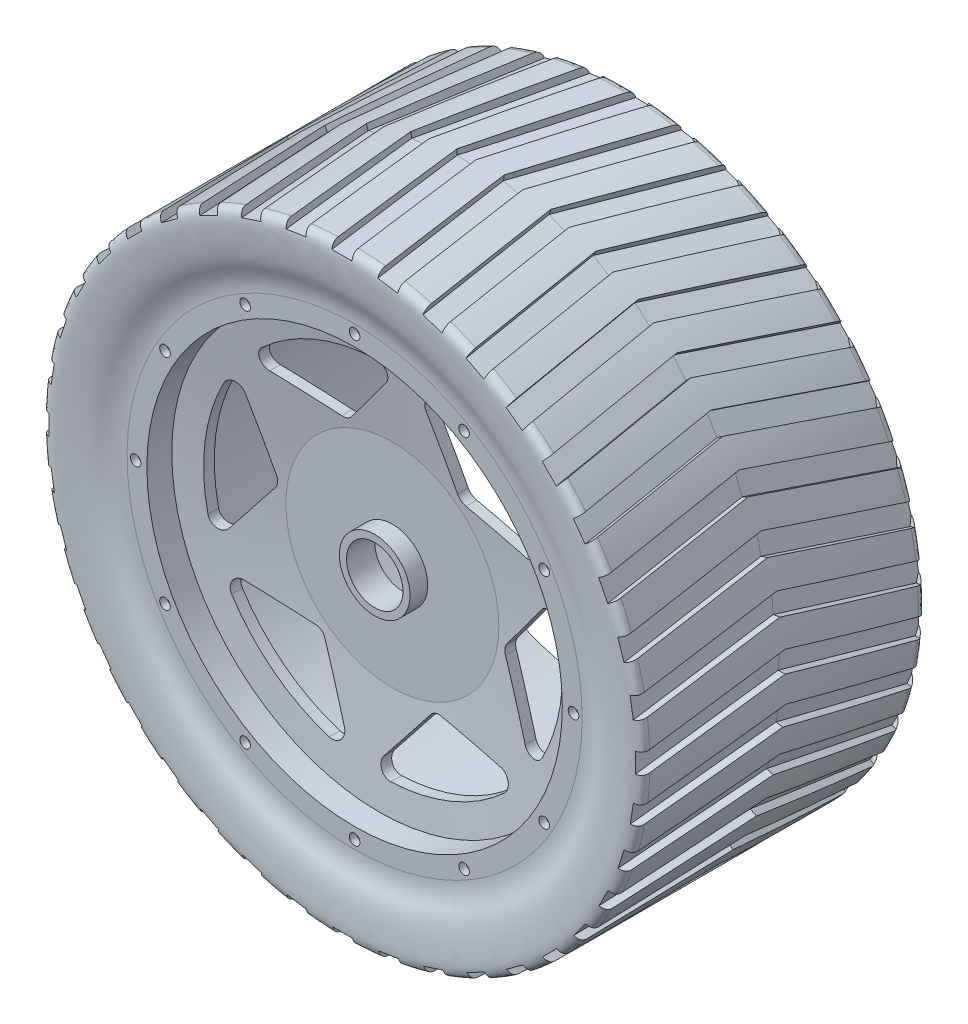
SolidWorks part; units mm, degrees
material "尼龙 101"
ref_plane "前视基准面" through (0, 0, 0) normal (0, 0, 1) x (1, 0, 0)
ref_plane "上视基准面" through (0, 0, 0) normal (0, 1, 0) x (1, 0, 0)
ref_plane "右视基准面" through (0, 0, 0) normal (1, 0, 0) x (0, 0, -1)
sketch "草图3" plane through (0, 0, 0) normal (1, 0, 0) x (0, 0, -1)
  line L4 (0, 0) -> (0, 30.1613)
  line L5 (0, 30.1613) -> (-3.6565, 58.8247)
  line L6 (-3.6565, 58.8247) -> (-10.6986, 58.8247)
  line L7 (-10.6986, 58.8247) -> (-10.6986, 64.4317)
  line L8 (-12.0785, 85) -> (63.9495, 85)
  line L9 (25.9355, 85) -> (25.9355, 104.8995) construction
  line L11 (62.5696, 64.4317) -> (-7.6986, 64.4317)
  line L12 (3, 0) -> (3, 30.3519)
  line L13 (3, 30.3519) -> (-1.0149, 61.8247)
  line L14 (-1.0149, 61.8247) -> (-7.6986, 61.8247)
  line L15 (-7.6986, 61.8247) -> (-7.6986, 64.4317)
  line L16 (0, 0) -> (3, 0)
  spline S0 degree 3 poles (-10.6986, 64.4317) (-10.6986, 68.3766) (-13.2297, 71.4024) (-13.9668, 77.8511) (-14.9063, 85) (-12.0785, 85) knots 0 0 0 0 0.38236 0.670208 1 1 1 1
  spline S1 degree 3 poles (62.5696, 64.4317) (62.5696, 68.3766) (65.1007, 71.4024) (65.8379, 77.8511) (66.7773, 85) (63.9495, 85) knots 0 0 0 0 0.38236 0.670208 1 1 1 1
  dimension "D2" = 85
  dimension "D1" = 3
revolve "旋转3" add sketch "草图3" angle 360 about L16
sketch "草图5" plane through (0, 0, 0) normal (0, 0, 1) x (1, 0, 0)
  circle A0 centre (0, 0) radius 8
  dimension "D1" = 16
extrude "切除-拉伸2" cut sketch "草图5" against normal blind 60
sketch "草图6" plane through (0, 0, 0) normal (0, 0, 1) x (1, 0, 0)
  circle A0 centre (0, 0) radius 10
  circle A1 centre (0, 0) radius 8 construction
  circle A2 centre (0, 0) radius 8
  dimension "D1" = 20
extrude "凸台-拉伸2" add sketch "草图6" along normal blind 5
sketch "草图7" plane through (0, 0, 10.6986) normal (0, 0, 1) x (1, 0, 0)
  line L0 (0, 0) -> (0, 68.4943) construction
  line L1 (0, 0) -> (73.4449, 19.6795) construction
  line L2 (8.7645, 51.2576) -> (19.4804, 25.3873)
  line L3 (47.2426, 21.7323) -> (19.4804, 25.3873)
  line L4 (19.4804, 25.3873) -> (0, 0) construction
  circle A0 centre (0, 0) radius 50.8247
  circle A2 centre (0, 0) radius 53.8247
  circle A3 centre (0, 0) radius 53.8247
  dimension "D1" = 75
  dimension "D2" = 37.5
  dimension "D4" = 32
  dimension "D6" = 120
  dimension "D3" = 5
  dimension "D5" = 3
extrude "切除-拉伸3" cut sketch "草图7" against normal through all contours L3 A0 L2 region at (26.3327, 34.3175, 10.6986)
fillet "圆角1" radius 3 3 edges at (45.8573, 21.9147, 1.1238) (9.2992, 49.9667, 1.1238) (19.4804, 25.3873, -1.2776)
pattern_circular "阵列(圆周)1" count 6 over 360 about axis through (0, 0, 10.6986) along (0, 0, 1) of "切除-拉伸3", "圆角1"
sketch "草图8" plane through (0, 0, 10.6986) normal (0, 0, 1) x (1, 0, 0)
  line L0 (0, 0) -> (0, 62) construction
  circle A0 centre (0, 62) radius 1.5
  dimension "D1" = 3
  dimension "D2" = 62
extrude "切除-拉伸4" cut sketch "草图8" against normal blind 2
pattern_circular "阵列(圆周)2" count 12 over 360 about axis through (0, 0, 3.6565) along (0, 0, -1) of "切除-拉伸4"
ref_plane "基准面2" through (0, 0, 15) normal (0, 0, 1) x (1, 0, 0)
sketch "草图9" plane through (0, 0, 15) normal (0, 0, 1) x (1, 0, 0)
  line L1 (-2.8414, 83.0125) -> (2.8414, 83.0125)
  line L2 (-2.8414, 83.0125) -> (-2.8414, 86.9875)
  line L3 (-2.8414, 86.9875) -> (2.8414, 86.9875)
  line L4 (2.8414, 83.0125) -> (2.8414, 86.9875)
  line L5 (-2.8414, 83.0125) -> (2.8414, 86.9875) construction
  line L6 (-2.8414, 86.9875) -> (2.8414, 83.0125) construction
  circle A0 centre (0, 0) radius 85 construction
  point P0 (0, 85)
ref_plane "基准面1" through (0, 85, 0) normal (0, 1, 0) x (1, 0, 0)
sketch "草图10" plane through (0, 85, 0) normal (0, 1, 0) x (1, 0, 0)
  line L0 (-5.4321, 26.4532) -> (0, -15)
  line L1 (-5.4321, 26.4532) -> (5.7966, 66.1968)
  line L2 (81.6004, 66.1968) -> (-81.6004, 66.1968) construction
sweep "切除-扫描1" cut profiles "草图9" path "草图10"
pattern_circular "阵列(圆周)3" count 40 over 360 about axis through (0, 0, 10.6986) along (0, 0, 1) of "切除-扫描1"
